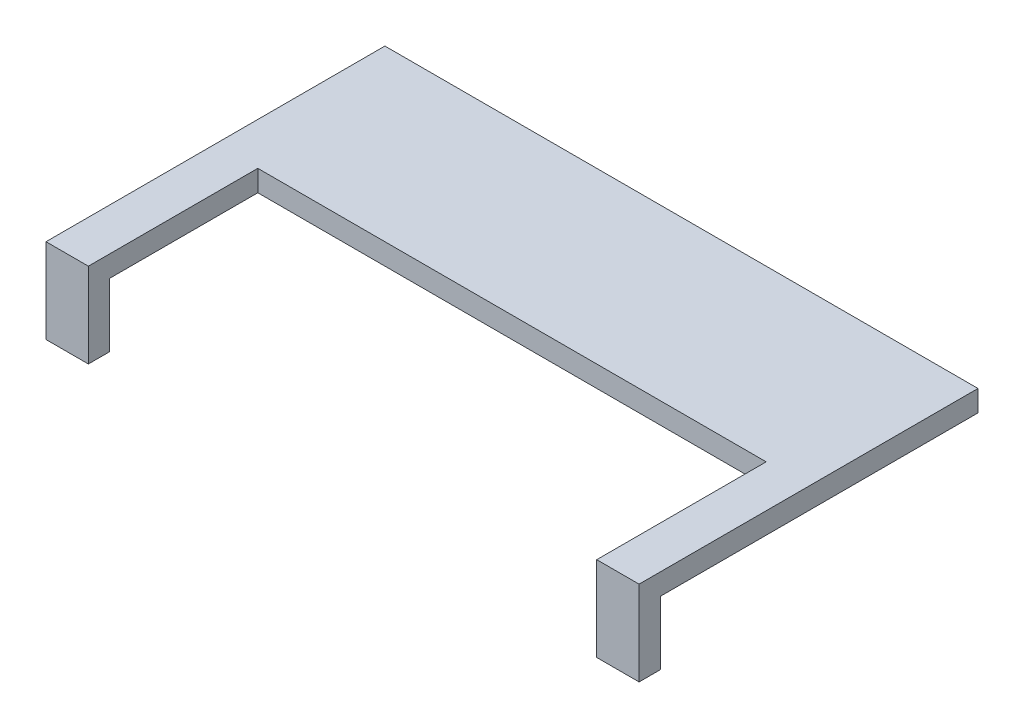
SolidWorks part; units mm, degrees
material "6061 Alloy"
ref_plane "Front Plane" through (0, 0, 0) normal (0, 0, 1) x (1, 0, 0)
ref_plane "Top Plane" through (0, 0, 0) normal (0, 1, 0) x (1, 0, 0)
ref_plane "Right Plane" through (0, 0, 0) normal (1, 0, 0) x (0, 0, -1)
sketch "Sketch1" plane through (0, 0, 0) normal (0, 1, 0) x (1, 0, 0)
  line L1 (-88.9, -50.8) -> (88.9, -50.8)
  line L2 (-88.9, -50.8) -> (-88.9, 50.8)
  line L3 (-88.9, 50.8) -> (88.9, 50.8)
  line L4 (88.9, -50.8) -> (88.9, 50.8)
  line L5 (-88.9, -50.8) -> (88.9, 50.8) construction
  line L6 (-88.9, 50.8) -> (88.9, -50.8) construction
  point P0 (0, 0)
  dimension "D1" = 101.6
  dimension "D2" = 177.8
extrude "Boss-Extrude1" add sketch "Sketch1" along normal blind 6.35
sketch "Sketch2" plane through (0, 0, 50.8) normal (0, 0, 1) x (1, 0, 0)
  line L1 (-88.9, 6.35) -> (-76.2, 6.35)
  line L2 (-88.9, 6.35) -> (-88.9, -19.05)
  line L3 (-88.9, -19.05) -> (-76.2, -19.05)
  line L4 (-76.2, 6.35) -> (-76.2, -19.05)
  dimension "D1" = 25.4
  dimension "D2" = 12.7
extrude "Boss-Extrude2" add sketch "Sketch2" against normal blind 6.35
mirror "Mirror1" about plane through (0, 0, 0) normal (1, 0, 0) of "Boss-Extrude2"
sketch "Sketch3" plane through (0, 6.35, 0) normal (0, 1, 0) x (1, 0, 0)
  line L0 (-88.9, -50.8) -> (88.9, -50.8) construction
  line L1 (-76.2, -50.8) -> (76.2, -50.8)
  line L2 (-76.2, -50.8) -> (-76.2, 0)
  line L3 (-76.2, 0) -> (76.2, 0)
  line L4 (76.2, -50.8) -> (76.2, 0)
  line L5 (-88.9, 50.8) -> (-88.9, -50.8) construction
  line L6 (88.9, -50.8) -> (88.9, 50.8) construction
  dimension "D1" = 50.8
  dimension "D2" = 12.7
  dimension "D3" = 12.7
extrude "Cut-Extrude1" cut sketch "Sketch3" against normal through all
